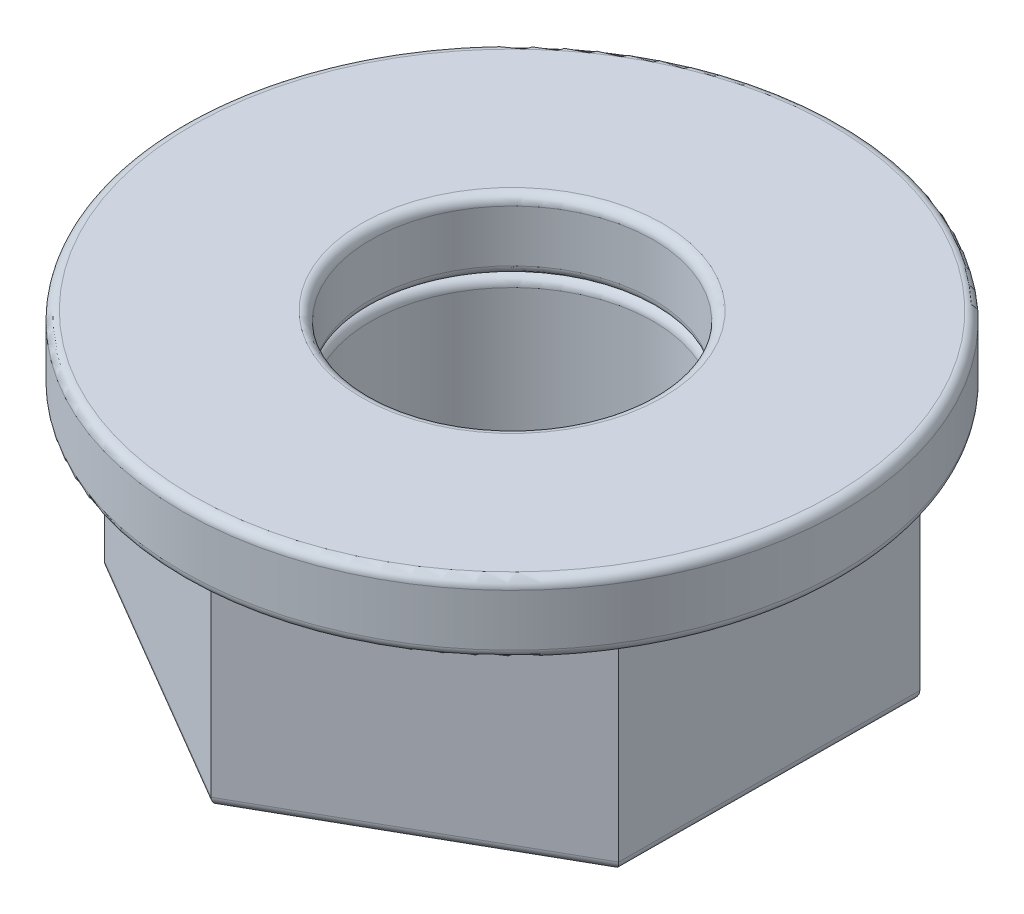
SolidWorks part; units mm, degrees
ref_plane "Front Plane" through (0, 0, 0) normal (0, 0, 1) x (1, 0, 0)
ref_plane "Top Plane" through (0, 0, 0) normal (0, 1, 0) x (1, 0, 0)
ref_plane "Right Plane" through (0, 0, 0) normal (1, 0, 0) x (0, 0, -1)
sketch "Sketch1" plane through (0, 0, 0) normal (0, 1, 0) x (1, 0, 0)
  line L1 (2.739, -1.6066) -> (2.7609, 1.5687)
  line L2 (2.7609, 1.5687) -> (0.0219, 3.1754)
  line L3 (0.0219, 3.1754) -> (-2.739, 1.6066)
  line L4 (-2.739, 1.6066) -> (-2.7609, -1.5687)
  line L5 (-2.7609, -1.5687) -> (-0.0219, -3.1754)
  line L6 (-0.0219, -3.1754) -> (2.739, -1.6066)
  circle A0 centre (0, 0) radius 2.75 construction
  circle A1 centre (0, 0) radius 1.5
  dimension "D1" = 5.5
  dimension "D2" = 3
extrude "Boss-Extrude1" add sketch "Sketch1" along normal blind 2.25
fillet "Fillet1" radius 0.1 14 edges at (0, 0, 1.5) (2.7499, 0, 0.0189) (1.3914, 0, -2.372) (-1.3586, 0, -2.391) (-2.7499, 0, -0.0189) (-1.3914, 0, 2.372) (1.3586, 0, 2.391) (0, 2.25, 1.5) (-1.3914, 2.25, 2.372) (-2.7499, 2.25, -0.0189) (-1.3586, 2.25, -2.391) (1.3914, 2.25, -2.372) (2.7499, 2.25, 0.0189) (1.3586, 2.25, 2.391)
sketch "Sketch2" plane through (0, 2.25, 0) normal (0, 1, 0) x (1, 0, 0)
  circle A0 centre (0, 0) radius 3.5
  circle A1 centre (0, 0) radius 1.5
  circle A2 centre (0, 0) radius 1.5 construction
  dimension "D1" = 7
extrude "Boss-Extrude2" add sketch "Sketch2" along normal blind 0.75
fillet "Fillet2" radius 0.1 4 edges at (0, 2.25, 1.5) (0, 3, 1.5) (0, 2.25, 3.5) (0, 3, 3.5)
